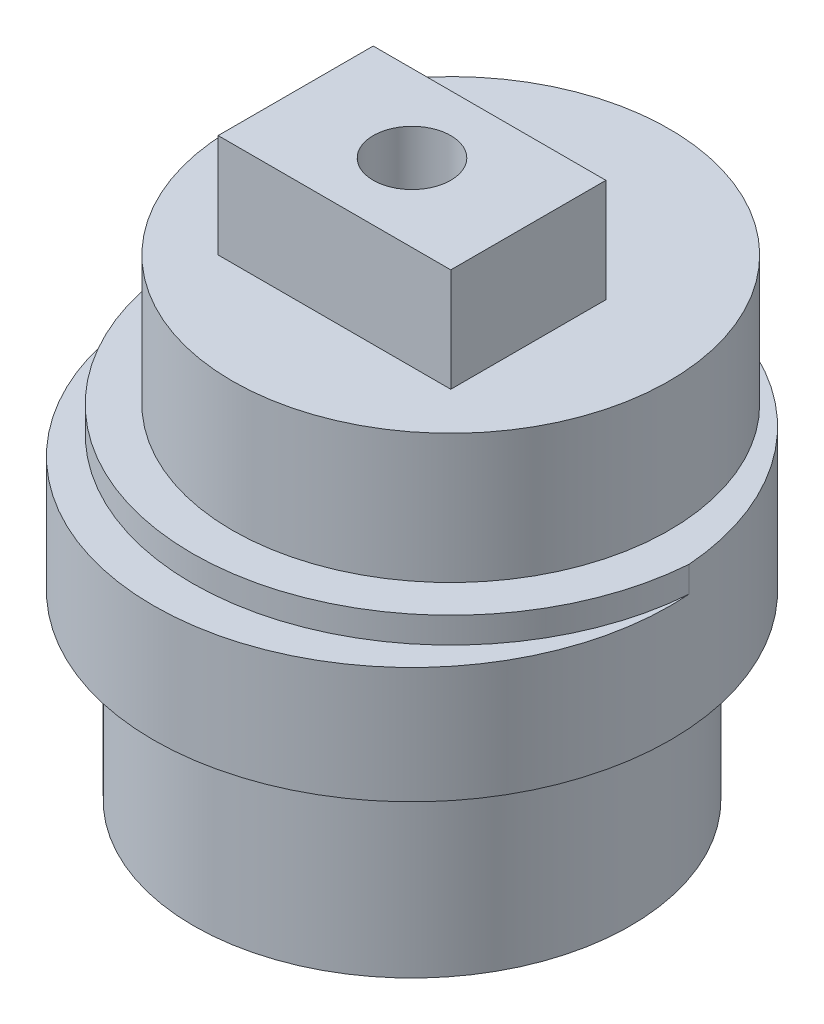
SolidWorks part; units mm, degrees
ref_plane "Front Plane" through (0, 0, 0) normal (0, 0, 1) x (1, 0, 0)
ref_plane "Top Plane" through (0, 0, 0) normal (0, 1, 0) x (1, 0, 0)
ref_plane "Right Plane" through (0, 0, 0) normal (1, 0, 0) x (0, 0, -1)
sketch "Sketch1" plane through (0, 0, 0) normal (0, 1, 0) x (1, 0, 0)
  circle A0 centre (0, 0) radius 8.45
  dimension "D1" = 16.9
extrude "Boss-Extrude1" add sketch "Sketch1" along normal blind 7
sketch "Sketch2" plane through (0, 7, 0) normal (0, 1, 0) x (1, 0, 0)
  circle A0 centre (0, 0) radius 10
  dimension "D1" = 20
extrude "Boss-Extrude2" add sketch "Sketch2" along normal blind 4.5
sketch "Sketch3" plane through (0, 11.5, 0) normal (0, 1, 0) x (1, 0, 0)
  circle A0 centre (0, 1.5) radius 8.45
  dimension "D1" = 16.9
  dimension "D2" = 1.5
extrude "Boss-Extrude3" add sketch "Sketch3" along normal blind 6
sketch "Sketch4" plane through (0, 11.5, 0) normal (0, 1, 0) x (1, 0, 0)
  circle A0 centre (0, 1.5) radius 8.45 construction
  circle A1 centre (0, 1.5) radius 8.45
  circle A2 centre (0, 0) radius 10 construction
  arc A3 (0, -10) -> (-9.9718, 0.75) centre (0, 0) ccw
  arc A4 (-9.9718, 0.75) -> (9.9718, 0.75) centre (0, 1.5) ccw
  arc A5 (9.9718, 0.75) -> (0, -10) centre (0, 0) ccw
  circle M1 centre (0, 1.5) radius 8.45
  circle M2 centre (0, 0) radius 10
  dimension "D1" = 20
extrude "Boss-Extrude4" add sketch "Sketch4" along normal blind 1 contours A4 M2 M1 region at (0, 11.5, -9.9728)
sketch "Sketch5" plane through (0, 17.5, 0) normal (0, 1, 0) x (1, 0, 0)
  line L1 (-4.5, -3) -> (4.5, -3)
  line L2 (-4.5, -3) -> (-4.5, 3)
  line L3 (-4.5, 3) -> (4.5, 3)
  line L4 (4.5, -3) -> (4.5, 3)
  line L5 (-4.5, -3) -> (4.5, 3) construction
  line L6 (-4.5, 3) -> (4.5, -3) construction
  point P2 (0, 0)
  dimension "D3" = 9
  dimension "D4" = 6
extrude "Boss-Extrude5" add sketch "Sketch5" along normal blind 4
sketch "Sketch6" plane through (0, 21.5, 0) normal (0, 1, 0) x (1, 0, 0)
  circle A0 centre (0, 0) radius 1.5
  dimension "D1" = 3
extrude "Cut-Extrude1" cut sketch "Sketch6" against normal blind 8
sketch "Sketch7" plane through (0, 0, 0) normal (0, -1, 0) x (-1, 0, 0)
  circle A0 centre (0, -5.5) radius 1.5
  circle A1 centre (-5.5, 0) radius 1.5
  circle A2 centre (0, 5.5) radius 1.5
  circle A3 centre (5.5, 0) radius 1.5
  point P12 (0, 0)
  dimension "D3" = 3
  dimension "D1" = 5.5
  dimension "D2" = 4
extrude "Cut-Extrude2" [suppressed] cut sketch "Sketch7" against normal blind 8
sketch "Sketch8" plane through (0, 0, 0) normal (0, -1, 0) x (1, 0, 0)
  arc A0 (1.9433, 2.9259) -> (1.4435, 3.2021) centre (0, 0) ccw
  arc A1 (-2.4201, 2.5457) -> (-2.8006, 2.1199) centre (0, 0) ccw
  arc A2 (3.4992, 0.3049) -> (3.4036, 0.8679) centre (0, 0) ccw
  arc A3 (2.4201, -2.5457) -> (2.8006, -2.1199) centre (0, 0) ccw
  arc A4 (-1.0759, 3.3436) -> (-1.6035, 3.1251) centre (0, 0) ccw
  arc A5 (-3.0204, -1.793) -> (-2.6899, -2.2587) centre (0, 0) ccw
  arc A6 (0.4814, 3.4793) -> (-0.0888, 3.5113) centre (0, 0) ccw
  arc A7 (3.0204, 1.793) -> (2.6899, 2.2587) centre (0, 0) ccw
  arc A8 (3.285, -1.2435) -> (3.4431, -0.6948) centre (0, 0) ccw
  arc A9 (-3.285, 1.2435) -> (-3.4431, 0.6948) centre (0, 0) ccw
  arc A10 (1.0759, -3.3436) -> (1.6035, -3.1251) centre (0, 0) ccw
  arc A11 (-1.9433, -2.9259) -> (-1.4435, -3.2021) centre (0, 0) ccw
  arc A12 (-0.4814, -3.4793) -> (0.0888, -3.5113) centre (0, 0) ccw
  arc A13 (-3.4992, -0.3049) -> (-3.4036, -0.8679) centre (0, 0) ccw
  spline S0 degree 3 poles (-2.6899, -2.2587) (-2.6998, -2.278) (-2.7192, -2.3185) (-2.7467, -2.3829) (-2.7734, -2.4537) (-2.7988, -2.5314) (-2.8225, -2.6162) (-2.8438, -2.7079) (-2.8627, -2.8065) (-2.877, -2.9191) (-2.8909, -3.0073) (-2.8865, -3.0684) (-2.8815, -3.0926) (-2.874, -3.1162) (-2.8635, -3.1386) (-2.8488, -3.1646) (-2.8257, -3.1852) (-2.7982, -3.1969) (-2.7748, -3.2048) (-2.7506, -3.2097) (-2.7259, -3.2119) (-2.6647, -3.2094) (-2.5786, -3.1858) (-2.4684, -3.1589) (-2.3725, -3.1291) (-2.2837, -3.0977) (-2.2021, -3.0646) (-2.1277, -3.0307) (-2.0604, -2.9963) (-1.9994, -2.9617) (-1.9614, -2.9379) (-1.9433, -2.9259) knots 0.027203 0.027203 0.027203 0.027203 0.059318 0.093556 0.130845 0.171187 0.214581 0.261026 0.310525 0.363075 0.429245 0.441417 0.453589 0.465761 0.477933 0.490104 0.509896 0.522067 0.534239 0.546411 0.558583 0.570755 0.636925 0.689475 0.738974 0.785419 0.828813 0.869155 0.906444 0.940682 0.972797 0.972797 0.972797 0.972797 weights 1 1 1 1 1 1 1 1 1 1 1 1 1 1 1 1 1 1 1 1 1 1 1 1 1 1 1 1 1 1 1 1
  spline S1 degree 3 poles (-1.6035, 3.1251) (-1.6202, 3.139) (-1.6552, 3.1669) (-1.7119, 3.2081) (-1.775, 3.2498) (-1.8451, 3.2919) (-1.9225, 3.3339) (-2.0072, 3.3751) (-2.0992, 3.4154) (-2.2057, 3.4545) (-2.2886, 3.4876) (-2.3492, 3.4969) (-2.3739, 3.4975) (-2.3985, 3.4953) (-2.4227, 3.4901) (-2.4514, 3.4815) (-2.4765, 3.4637) (-2.4941, 3.4395) (-2.507, 3.4184) (-2.5172, 3.3958) (-2.5248, 3.3723) (-2.536, 3.312) (-2.5321, 3.2229) (-2.5304, 3.1094) (-2.5227, 3.0093) (-2.5119, 2.9157) (-2.4978, 2.8289) (-2.4812, 2.7487) (-2.4627, 2.6754) (-2.4425, 2.6083) (-2.4278, 2.566) (-2.4201, 2.5457) knots 0.027203 0.027203 0.027203 0.027203 0.059318 0.093556 0.130845 0.171187 0.214581 0.261026 0.310525 0.363075 0.429245 0.441417 0.453589 0.465761 0.477933 0.490104 0.509896 0.522067 0.534239 0.546411 0.558583 0.570755 0.636925 0.689475 0.738974 0.785419 0.828813 0.869155 0.906444 0.940682 0.972797 0.972797 0.972797 0.972797 weights 1 1 1 1 1 1 1 1 1 1 1 1 1 1 1 1 1 1 1 1 1 1 1 1 1 1 1 1 1 1 1 1
  spline S2 degree 3 poles (2.6899, 2.2587) (2.6998, 2.278) (2.7192, 2.3185) (2.7467, 2.3829) (2.7734, 2.4537) (2.7988, 2.5314) (2.8225, 2.6162) (2.8438, 2.7079) (2.8627, 2.8065) (2.877, 2.9191) (2.8909, 3.0073) (2.8865, 3.0684) (2.8815, 3.0926) (2.874, 3.1162) (2.8635, 3.1386) (2.8488, 3.1646) (2.8257, 3.1852) (2.7982, 3.1969) (2.7748, 3.2048) (2.7506, 3.2097) (2.7259, 3.2119) (2.6647, 3.2094) (2.5786, 3.1858) (2.4684, 3.1589) (2.3725, 3.1291) (2.2837, 3.0977) (2.2021, 3.0646) (2.1277, 3.0307) (2.0604, 2.9963) (1.9994, 2.9617) (1.9614, 2.9379) (1.9433, 2.9259) knots 0.027203 0.027203 0.027203 0.027203 0.059318 0.093556 0.130845 0.171187 0.214581 0.261026 0.310525 0.363075 0.429245 0.441417 0.453589 0.465761 0.477933 0.490104 0.509896 0.522067 0.534239 0.546411 0.558583 0.570755 0.636925 0.689475 0.738974 0.785419 0.828813 0.869155 0.906444 0.940682 0.972797 0.972797 0.972797 0.972797 weights 1 1 1 1 1 1 1 1 1 1 1 1 1 1 1 1 1 1 1 1 1 1 1 1 1 1 1 1 1 1 1 1
  spline S3 degree 3 poles (3.4036, 0.8679) (3.4208, 0.881) (3.4559, 0.909) (3.5086, 0.9551) (3.5633, 1.0074) (3.62, 1.0664) (3.6781, 1.1324) (3.7371, 1.2058) (3.7969, 1.2865) (3.8587, 1.3817) (3.9094, 1.4551) (3.9319, 1.5121) (3.938, 1.5361) (3.9414, 1.5606) (3.9417, 1.5853) (3.9397, 1.6152) (3.9279, 1.6437) (3.9082, 1.6662) (3.8905, 1.6835) (3.8708, 1.6984) (3.8495, 1.7111) (3.7933, 1.7354) (3.7055, 1.7515) (3.5945, 1.7751) (3.4952, 1.7899) (3.4016, 1.8001) (3.3137, 1.8057) (3.232, 1.8073) (3.1564, 1.8056) (3.0865, 1.8009) (3.0419, 1.7959) (3.0204, 1.793) knots 0.027203 0.027203 0.027203 0.027203 0.059318 0.093556 0.130845 0.171187 0.214581 0.261026 0.310525 0.363075 0.429245 0.441417 0.453589 0.465761 0.477933 0.490104 0.509896 0.522067 0.534239 0.546411 0.558583 0.570755 0.636925 0.689475 0.738974 0.785419 0.828813 0.869155 0.906444 0.940682 0.972797 0.972797 0.972797 0.972797 weights 1 1 1 1 1 1 1 1 1 1 1 1 1 1 1 1 1 1 1 1 1 1 1 1 1 1 1 1 1 1 1 1
  spline S4 degree 3 poles (2.8006, -2.1199) (2.8217, -2.1252) (2.8654, -2.1351) (2.9343, -2.1476) (3.0093, -2.1578) (3.0907, -2.1653) (3.1786, -2.1696) (3.2728, -2.1699) (3.3732, -2.1664) (3.4861, -2.1553) (3.5751, -2.1492) (3.6338, -2.1313) (3.6563, -2.1211) (3.6776, -2.1085) (3.6971, -2.0933) (3.7192, -2.0731) (3.7341, -2.0461) (3.7394, -2.0167) (3.7419, -1.9921) (3.7413, -1.9674) (3.7379, -1.9429) (3.7219, -1.8837) (3.6797, -1.8051) (3.629, -1.7036) (3.5786, -1.6167) (3.5282, -1.5371) (3.4778, -1.465) (3.4281, -1.4) (3.3796, -1.342) (3.3324, -1.2903) (3.3007, -1.2585) (3.285, -1.2435) knots 0.027203 0.027203 0.027203 0.027203 0.059318 0.093556 0.130845 0.171187 0.214581 0.261026 0.310525 0.363075 0.429245 0.441417 0.453589 0.465761 0.477933 0.490104 0.509896 0.522067 0.534239 0.546411 0.558583 0.570755 0.636925 0.689475 0.738974 0.785419 0.828813 0.869155 0.906444 0.940682 0.972797 0.972797 0.972797 0.972797 weights 1 1 1 1 1 1 1 1 1 1 1 1 1 1 1 1 1 1 1 1 1 1 1 1 1 1 1 1 1 1 1 1
  spline S5 degree 3 poles (-2.8006, 2.1199) (-2.8217, 2.1252) (-2.8654, 2.1351) (-2.9343, 2.1476) (-3.0093, 2.1578) (-3.0907, 2.1653) (-3.1786, 2.1696) (-3.2728, 2.1699) (-3.3732, 2.1664) (-3.4861, 2.1553) (-3.5751, 2.1492) (-3.6338, 2.1313) (-3.6563, 2.1211) (-3.6776, 2.1085) (-3.6971, 2.0933) (-3.7192, 2.0731) (-3.7341, 2.0461) (-3.7394, 2.0167) (-3.7419, 1.9921) (-3.7413, 1.9674) (-3.7379, 1.9429) (-3.7219, 1.8837) (-3.6797, 1.8051) (-3.629, 1.7036) (-3.5786, 1.6167) (-3.5282, 1.5371) (-3.4778, 1.465) (-3.4281, 1.4) (-3.3796, 1.342) (-3.3324, 1.2903) (-3.3007, 1.2585) (-3.285, 1.2435) knots 0.027203 0.027203 0.027203 0.027203 0.059318 0.093556 0.130845 0.171187 0.214581 0.261026 0.310525 0.363075 0.429245 0.441417 0.453589 0.465761 0.477933 0.490104 0.509896 0.522067 0.534239 0.546411 0.558583 0.570755 0.636925 0.689475 0.738974 0.785419 0.828813 0.869155 0.906444 0.940682 0.972797 0.972797 0.972797 0.972797 weights 1 1 1 1 1 1 1 1 1 1 1 1 1 1 1 1 1 1 1 1 1 1 1 1 1 1 1 1 1 1 1 1
  spline S6 degree 3 poles (1.4435, 3.2021) (1.444, 3.2238) (1.444, 3.2687) (1.4408, 3.3387) (1.4341, 3.414) (1.4233, 3.4951) (1.4079, 3.5817) (1.3873, 3.6736) (1.3615, 3.7707) (1.3256, 3.8783) (1.2998, 3.9638) (1.2693, 4.0169) (1.2543, 4.0366) (1.2373, 4.0546) (1.2182, 4.0702) (1.1936, 4.0872) (1.1639, 4.0958) (1.134, 4.0944) (1.1095, 4.0914) (1.0855, 4.0852) (1.0624, 4.0765) (1.0083, 4.0478) (0.941, 3.9891) (0.8533, 3.9171) (0.7798, 3.8486) (0.7135, 3.7818) (0.6543, 3.7166) (0.6021, 3.6537) (0.5563, 3.5935) (0.5164, 3.5359) (0.4925, 3.498) (0.4814, 3.4793) knots 0.027203 0.027203 0.027203 0.027203 0.059318 0.093556 0.130845 0.171187 0.214581 0.261026 0.310525 0.363075 0.429245 0.441417 0.453589 0.465761 0.477933 0.490104 0.509896 0.522067 0.534239 0.546411 0.558583 0.570755 0.636925 0.689475 0.738974 0.785419 0.828813 0.869155 0.906444 0.940682 0.972797 0.972797 0.972797 0.972797 weights 1 1 1 1 1 1 1 1 1 1 1 1 1 1 1 1 1 1 1 1 1 1 1 1 1 1 1 1 1 1 1 1
  spline S7 degree 3 poles (-1.4435, -3.2021) (-1.444, -3.2238) (-1.444, -3.2687) (-1.4408, -3.3387) (-1.4341, -3.414) (-1.4233, -3.4951) (-1.4079, -3.5817) (-1.3873, -3.6736) (-1.3615, -3.7707) (-1.3256, -3.8783) (-1.2998, -3.9638) (-1.2693, -4.0169) (-1.2543, -4.0366) (-1.2373, -4.0546) (-1.2182, -4.0702) (-1.1936, -4.0872) (-1.1639, -4.0958) (-1.134, -4.0944) (-1.1095, -4.0914) (-1.0855, -4.0852) (-1.0624, -4.0765) (-1.0083, -4.0478) (-0.941, -3.9891) (-0.8533, -3.9171) (-0.7798, -3.8486) (-0.7135, -3.7818) (-0.6543, -3.7166) (-0.6021, -3.6537) (-0.5563, -3.5935) (-0.5164, -3.5359) (-0.4925, -3.498) (-0.4814, -3.4793) knots 0.027203 0.027203 0.027203 0.027203 0.059318 0.093556 0.130845 0.171187 0.214581 0.261026 0.310525 0.363075 0.429245 0.441417 0.453589 0.465761 0.477933 0.490104 0.509896 0.522067 0.534239 0.546411 0.558583 0.570755 0.636925 0.689475 0.738974 0.785419 0.828813 0.869155 0.906444 0.940682 0.972797 0.972797 0.972797 0.972797 weights 1 1 1 1 1 1 1 1 1 1 1 1 1 1 1 1 1 1 1 1 1 1 1 1 1 1 1 1 1 1 1 1
  spline S8 degree 3 poles (-3.4036, -0.8679) (-3.4208, -0.881) (-3.4559, -0.909) (-3.5086, -0.9551) (-3.5633, -1.0074) (-3.62, -1.0664) (-3.6781, -1.1324) (-3.7371, -1.2058) (-3.7969, -1.2865) (-3.8587, -1.3817) (-3.9094, -1.4551) (-3.9319, -1.5121) (-3.938, -1.5361) (-3.9414, -1.5606) (-3.9417, -1.5853) (-3.9397, -1.6152) (-3.9279, -1.6437) (-3.9082, -1.6662) (-3.8905, -1.6835) (-3.8708, -1.6984) (-3.8495, -1.7111) (-3.7933, -1.7354) (-3.7055, -1.7515) (-3.5945, -1.7751) (-3.4952, -1.7899) (-3.4016, -1.8001) (-3.3137, -1.8057) (-3.232, -1.8073) (-3.1564, -1.8056) (-3.0865, -1.8009) (-3.0419, -1.7959) (-3.0204, -1.793) knots 0.027203 0.027203 0.027203 0.027203 0.059318 0.093556 0.130845 0.171187 0.214581 0.261026 0.310525 0.363075 0.429245 0.441417 0.453589 0.465761 0.477933 0.490104 0.509896 0.522067 0.534239 0.546411 0.558583 0.570755 0.636925 0.689475 0.738974 0.785419 0.828813 0.869155 0.906444 0.940682 0.972797 0.972797 0.972797 0.972797 weights 1 1 1 1 1 1 1 1 1 1 1 1 1 1 1 1 1 1 1 1 1 1 1 1 1 1 1 1 1 1 1 1
  spline S9 degree 3 poles (3.4431, -0.6948) (3.4643, -0.6905) (3.508, -0.6804) (3.5756, -0.6618) (3.6475, -0.6385) (3.7242, -0.6099) (3.8052, -0.5756) (3.8902, -0.535) (3.9791, -0.4883) (4.0761, -0.4293) (4.1536, -0.3852) (4.1987, -0.3436) (4.2145, -0.3246) (4.2282, -0.304) (4.2392, -0.2819) (4.2504, -0.2541) (4.2521, -0.2233) (4.2441, -0.1945) (4.2357, -0.1713) (4.2244, -0.1493) (4.2107, -0.1286) (4.1706, -0.0823) (4.0985, -0.0298) (4.0087, 0.0397) (3.9256, 0.0961) (3.8457, 0.1459) (3.769, 0.1891) (3.6961, 0.2261) (3.6272, 0.2573) (3.5622, 0.2834) (3.5199, 0.2982) (3.4992, 0.3049) knots 0.027203 0.027203 0.027203 0.027203 0.059318 0.093556 0.130845 0.171187 0.214581 0.261026 0.310525 0.363075 0.429245 0.441417 0.453589 0.465761 0.477933 0.490104 0.509896 0.522067 0.534239 0.546411 0.558583 0.570755 0.636925 0.689475 0.738974 0.785419 0.828813 0.869155 0.906444 0.940682 0.972797 0.972797 0.972797 0.972797 weights 1 1 1 1 1 1 1 1 1 1 1 1 1 1 1 1 1 1 1 1 1 1 1 1 1 1 1 1 1 1 1 1
  spline S10 degree 3 poles (-0.0888, 3.5113) (-0.0977, 3.5311) (-0.1172, 3.5715) (-0.1505, 3.6332) (-0.1892, 3.6981) (-0.2341, 3.7665) (-0.2856, 3.8379) (-0.344, 3.9117) (-0.4094, 3.988) (-0.4885, 4.0694) (-0.5487, 4.1352) (-0.5993, 4.1698) (-0.6213, 4.1811) (-0.6444, 4.1899) (-0.6685, 4.1957) (-0.698, 4.2003) (-0.7284, 4.1952) (-0.7548, 4.181) (-0.7755, 4.1676) (-0.7945, 4.1517) (-0.8116, 4.1338) (-0.8478, 4.0844) (-0.883, 4.0024) (-0.9307, 3.8994) (-0.9672, 3.8058) (-0.998, 3.7168) (-1.023, 3.6325) (-1.0429, 3.5531) (-1.058, 3.479) (-1.0689, 3.4098) (-1.074, 3.3652) (-1.0759, 3.3436) knots 0.027203 0.027203 0.027203 0.027203 0.059318 0.093556 0.130845 0.171187 0.214581 0.261026 0.310525 0.363075 0.429245 0.441417 0.453589 0.465761 0.477933 0.490104 0.509896 0.522067 0.534239 0.546411 0.558583 0.570755 0.636925 0.689475 0.738974 0.785419 0.828813 0.869155 0.906444 0.940682 0.972797 0.972797 0.972797 0.972797 weights 1 1 1 1 1 1 1 1 1 1 1 1 1 1 1 1 1 1 1 1 1 1 1 1 1 1 1 1 1 1 1 1
  spline S11 degree 3 poles (1.6035, -3.1251) (1.6202, -3.139) (1.6552, -3.1669) (1.7119, -3.2081) (1.775, -3.2498) (1.8451, -3.2919) (1.9225, -3.3339) (2.0072, -3.3751) (2.0992, -3.4154) (2.2057, -3.4545) (2.2886, -3.4876) (2.3492, -3.4969) (2.3739, -3.4975) (2.3985, -3.4953) (2.4227, -3.4901) (2.4514, -3.4815) (2.4765, -3.4637) (2.4941, -3.4395) (2.507, -3.4184) (2.5172, -3.3958) (2.5248, -3.3723) (2.536, -3.312) (2.5321, -3.2229) (2.5304, -3.1094) (2.5227, -3.0093) (2.5119, -2.9157) (2.4978, -2.8289) (2.4812, -2.7487) (2.4627, -2.6754) (2.4425, -2.6083) (2.4278, -2.566) (2.4201, -2.5457) knots 0.027203 0.027203 0.027203 0.027203 0.059318 0.093556 0.130845 0.171187 0.214581 0.261026 0.310525 0.363075 0.429245 0.441417 0.453589 0.465761 0.477933 0.490104 0.509896 0.522067 0.534239 0.546411 0.558583 0.570755 0.636925 0.689475 0.738974 0.785419 0.828813 0.869155 0.906444 0.940682 0.972797 0.972797 0.972797 0.972797 weights 1 1 1 1 1 1 1 1 1 1 1 1 1 1 1 1 1 1 1 1 1 1 1 1 1 1 1 1 1 1 1 1
  spline S12 degree 3 poles (-3.4431, 0.6948) (-3.4643, 0.6905) (-3.508, 0.6804) (-3.5756, 0.6618) (-3.6475, 0.6385) (-3.7242, 0.6099) (-3.8052, 0.5756) (-3.8902, 0.535) (-3.9791, 0.4883) (-4.0761, 0.4293) (-4.1536, 0.3852) (-4.1987, 0.3436) (-4.2145, 0.3246) (-4.2282, 0.304) (-4.2392, 0.2819) (-4.2504, 0.2541) (-4.2521, 0.2233) (-4.2441, 0.1945) (-4.2357, 0.1713) (-4.2244, 0.1493) (-4.2107, 0.1286) (-4.1706, 0.0823) (-4.0985, 0.0298) (-4.0087, -0.0397) (-3.9256, -0.0961) (-3.8457, -0.1459) (-3.769, -0.1891) (-3.6961, -0.2261) (-3.6272, -0.2573) (-3.5622, -0.2834) (-3.5199, -0.2982) (-3.4992, -0.3049) knots 0.027203 0.027203 0.027203 0.027203 0.059318 0.093556 0.130845 0.171187 0.214581 0.261026 0.310525 0.363075 0.429245 0.441417 0.453589 0.465761 0.477933 0.490104 0.509896 0.522067 0.534239 0.546411 0.558583 0.570755 0.636925 0.689475 0.738974 0.785419 0.828813 0.869155 0.906444 0.940682 0.972797 0.972797 0.972797 0.972797 weights 1 1 1 1 1 1 1 1 1 1 1 1 1 1 1 1 1 1 1 1 1 1 1 1 1 1 1 1 1 1 1 1
  spline S13 degree 3 poles (0.0888, -3.5113) (0.0977, -3.5311) (0.1172, -3.5715) (0.1505, -3.6332) (0.1892, -3.6981) (0.2341, -3.7665) (0.2856, -3.8379) (0.344, -3.9117) (0.4094, -3.988) (0.4885, -4.0694) (0.5487, -4.1352) (0.5993, -4.1698) (0.6213, -4.1811) (0.6444, -4.1899) (0.6685, -4.1957) (0.698, -4.2003) (0.7284, -4.1952) (0.7548, -4.181) (0.7755, -4.1676) (0.7945, -4.1517) (0.8116, -4.1338) (0.8478, -4.0844) (0.883, -4.0024) (0.9307, -3.8994) (0.9672, -3.8058) (0.998, -3.7168) (1.023, -3.6325) (1.0429, -3.5531) (1.058, -3.479) (1.0689, -3.4098) (1.074, -3.3652) (1.0759, -3.3436) knots 0.027203 0.027203 0.027203 0.027203 0.059318 0.093556 0.130845 0.171187 0.214581 0.261026 0.310525 0.363075 0.429245 0.441417 0.453589 0.465761 0.477933 0.490104 0.509896 0.522067 0.534239 0.546411 0.558583 0.570755 0.636925 0.689475 0.738974 0.785419 0.828813 0.869155 0.906444 0.940682 0.972797 0.972797 0.972797 0.972797 weights 1 1 1 1 1 1 1 1 1 1 1 1 1 1 1 1 1 1 1 1 1 1 1 1 1 1 1 1 1 1 1 1
extrude "Cut-Extrude3" cut sketch "Sketch8" against normal blind 16
